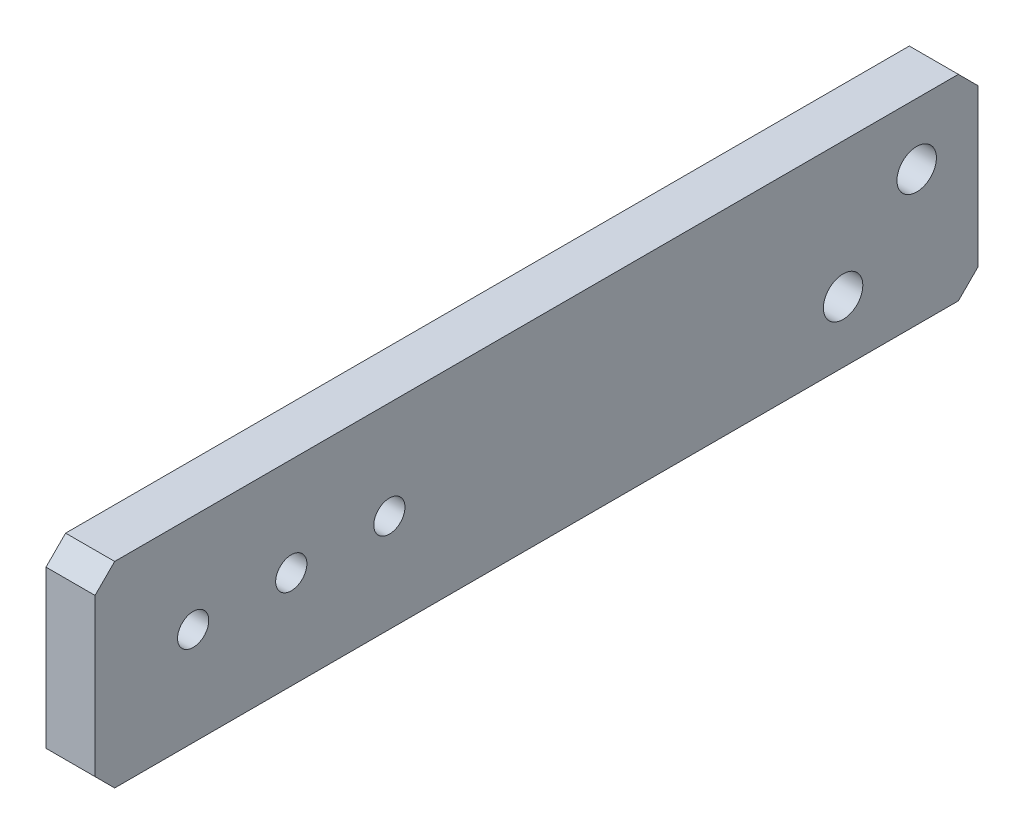
SolidWorks part; units mm, degrees
material "6061-T6 (SS)"
ref_plane "Front" through (0, 0, 0) normal (0, 0, 1) x (1, 0, 0)
ref_plane "Top" through (0, 0, 0) normal (0, 1, 0) x (1, 0, 0)
ref_plane "Right" through (0, 0, 0) normal (1, 0, 0) x (0, 0, -1)
sketch "Sketch1" plane through (0, 0, 0) normal (1, 0, 0) x (0, 0, -1)
  line L1 (0, 0) -> (114.3, 0)
  line L2 (0, 0) -> (0, 25.4)
  line L3 (0, 25.4) -> (114.3, 25.4)
  line L6 (114.3, 25.4) -> (114.3, 0)
  dimension "D1" = 25.4
  dimension "D2" = 114.3
extrude "Boss-Extrude1" add sketch "Sketch1" along normal blind 6.35
hole_wizard "#10-32 Tapped Hole1" positions "Sketch2" profile "Sketch3" tap size "#10-32" standard "ANSI Inch" end condition through all
sketch "Sketch2" plane through (6.35, 0, 0) normal (1, 0, 0) x (0, 0, -1)
  line L0 (0, 0) -> (12.7, 12.7) construction
  line L1 (12.7, 12.7) -> (25.4, 12.7) construction
  line L2 (25.4, 12.7) -> (38.1, 12.7) construction
  line L3 (38.1, 12.7) -> (50.8, 25.4) construction
  line L4 (114.3, 25.4) -> (0, 25.4) construction
  line L6 (0, 25.4) -> (0, 0) construction
  point P0 (12.7, 12.7)
  point P2 (25.4, 12.7)
  point P4 (38.1, 12.7)
  dimension "D1" = 50.8
  dimension "D2" = 12.7
sketch "Sketch3" plane through (6.35, 12.7, -12.7) normal (0, 1, 0) x (0, 0, -1)
  line L0 (0, 0) -> (0, 6.35)
  line L1 (0, 6.35) -> (2.0193, 6.35)
  line L2 (2.0193, 6.35) -> (2.0193, 0)
  line L5 (2.0193, 0) -> (0, 0)
  line L11 (0, -6.35) -> (0, 107.95) construction
  dimension "Thru Tap Drill Dia." = 4.0386
  dimension "Thru Tap Drill Depth" = 6.35
cosmetic thread "Hole Thread1"
cosmetic thread "Hole Thread2"
cosmetic thread "Hole Thread3"
hole_wizard "#10 Clearance Hole1" positions "Sketch4" profile "Sketch5" hole size "#10" standard "ANSI Inch" end condition through all
sketch "Sketch4" plane through (6.35, 0, 0) normal (1, 0, 0) x (0, 0, -1)
  line L0 (88.9, 0) -> (96.8375, 7.9375) construction
  line L1 (0, 0) -> (114.3, 0) construction
  line L2 (96.8375, 7.9375) -> (106.3625, 17.4625) construction
  line L3 (106.3625, 17.4625) -> (114.3, 25.4) construction
  line L5 (114.3, 0) -> (114.3, 25.4) construction
  point P13 (106.3625, 17.4625)
  point P15 (96.8375, 7.9375)
  dimension "D1" = 25.4
  dimension "D2" = 9.525
sketch "Sketch5" plane through (6.35, 17.4625, -106.3625) normal (0, 1, 0) x (0, 0, -1)
  line L0 (0, 0) -> (0, 6.35)
  line L1 (0, 6.35) -> (2.5527, 6.35)
  line L2 (2.5527, 6.35) -> (2.5527, 0)
  line L5 (2.5527, 0) -> (0, 0)
  line L11 (0, -6.35) -> (0, 107.95) construction
  dimension "Thru Hole Dia." = 5.1054
  dimension "Thru Hole Depth" = 6.35
chamfer "Chamfer1" distance 2.54 angle 45 4 edges at (3.175, 25.4, 0) (3.175, 25.4, -114.3) (3.175, 0, -114.3) (3.175, 0, 0)
